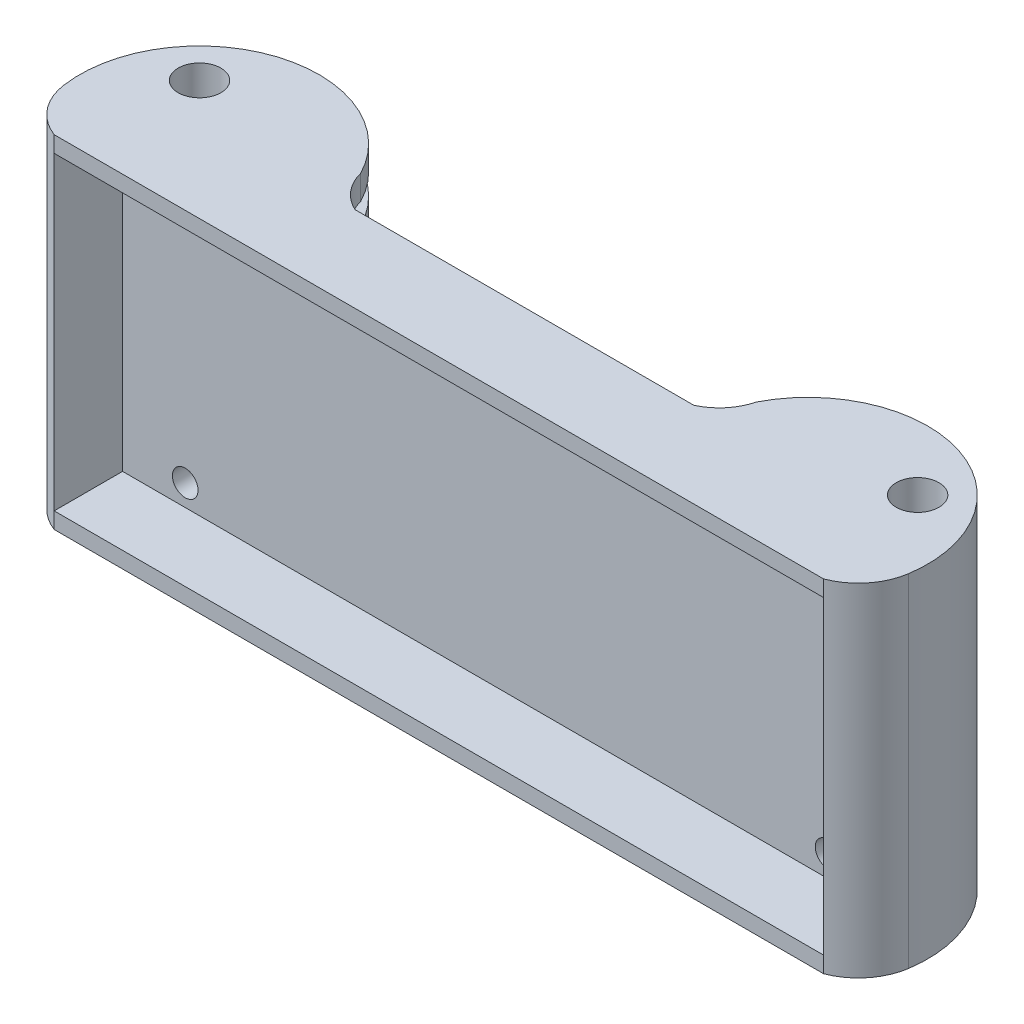
SolidWorks part; units mm, degrees
note: The reader was unsure of these and kept them because the rebuilt part matched: shared geometry of "Sketch3<5>".
ref_plane "Front Plane" through (0, 0, 0) normal (0, 0, 1) x (1, 0, 0)
ref_plane "Top Plane" through (0, 0, 0) normal (0, 1, 0) x (1, 0, 0)
ref_plane "Right Plane" through (0, 0, 0) normal (1, 0, 0) x (0, 0, -1)
sketch "Sketch1" plane through (0, 0, 0) normal (0, 1, 0) x (1, 0, 0)
  line L0 (-1190.4762, 0) -> (58333.3333, 0) construction
  line L1 (0, -1190.4762) -> (0, 58333.3333) construction
  line L2 (-45, -14) -> (45, -14)
  line L3 (19.8108, -4) -> (-19.8108, -4)
  circle A21 centre (-42, 0) radius 2.5
  arc A25 (-45, -14) -> (-49.4434, -8.493) centre (-42.521, -7.4537) cw
  arc A26 (-49.4434, -8.493) -> (-23.1545, 0) centre (-35.5986, -6.4143) cw
  circle A29 centre (42, 0) radius 2.5
  arc A30 (45, -14) -> (49.4434, -8.493) centre (42.521, -7.4537) ccw
  arc A32 (49.4434, -8.493) -> (23.1545, 0) centre (35.5986, -6.4143) ccw
  arc A33 (-19.8108, -4) -> (-23.1545, 0) centre (-17.3363, 1.466) cw
  arc A34 (19.8108, -4) -> (23.1545, 0) centre (17.3363, 1.466) ccw
  dimension "D2" = 6
  dimension "D3" = 90
  dimension "D4" = 10
  dimension "D5" = 4
  dimension "D10" = 5
  dimension "D11" = 14
  dimension "D12" = 7
  dimension "D8" = 42
extrude "Boss-Extrude2" add sketch "Sketch1" along normal blind 40
sketch "Sketch3" plane through (0, 0, 14) normal (0, 0, 1) x (1, 0, 0)
  line L0 (-59.1289, 20) -> (59.1289, 20) construction
  line L1 (0, 54.8983) -> (0, -14.8983) construction
  line L2 (-45, 40) -> (45, 40) construction
  line L7 (-45, 38.11) -> (45, 38.11)
  line L9 (-45, 40) -> (-45, 0) construction
  line L10 (45, 40) -> (45, 0) construction
  line L11 (45, 38.11) -> (45, 1.89)
  line L12 (-45, 1.89) -> (45, 1.89)
  line L13 (-45, 38.11) -> (-45, 1.89)
  line L17 (4.9276, 37.1479) -> (4.9276, 34.6879)
  line L18 (-35.0724, 37.1479) -> (4.9276, 37.1479)
  line L19 (-35.0724, 34.6879) -> (-35.0724, 37.1479)
  line L20 (4.9276, 34.6879) -> (-35.0724, 34.6879)
  circle A4 centre (37.5276, 35.8021) radius 1.5
  circle A5 centre (-37.6724, 35.8021) radius 1.5
  circle A6 centre (-37.6724, 4.3821) radius 1.5
  circle A7 centre (37.5276, 4.3821) radius 1.5
  point P3 (0, 20)
  point P7 (0, 20)
  dimension "D1" = 20
  dimension "D3" = 18.11
extrude "Cut-Extrude1" cut sketch "Sketch3" against normal blind 8
extrude "Cut-Extrude3" cut sketch "Sketch3<5>" against normal through all contours L20 L17 L18 L19 | A5 | A6 | A7 | A4
sketch "Sketch3<5>" plane through (0, 0, 14) normal (0, 0, 1) x (1, 0, 0) same geometry as "Sketch3"
